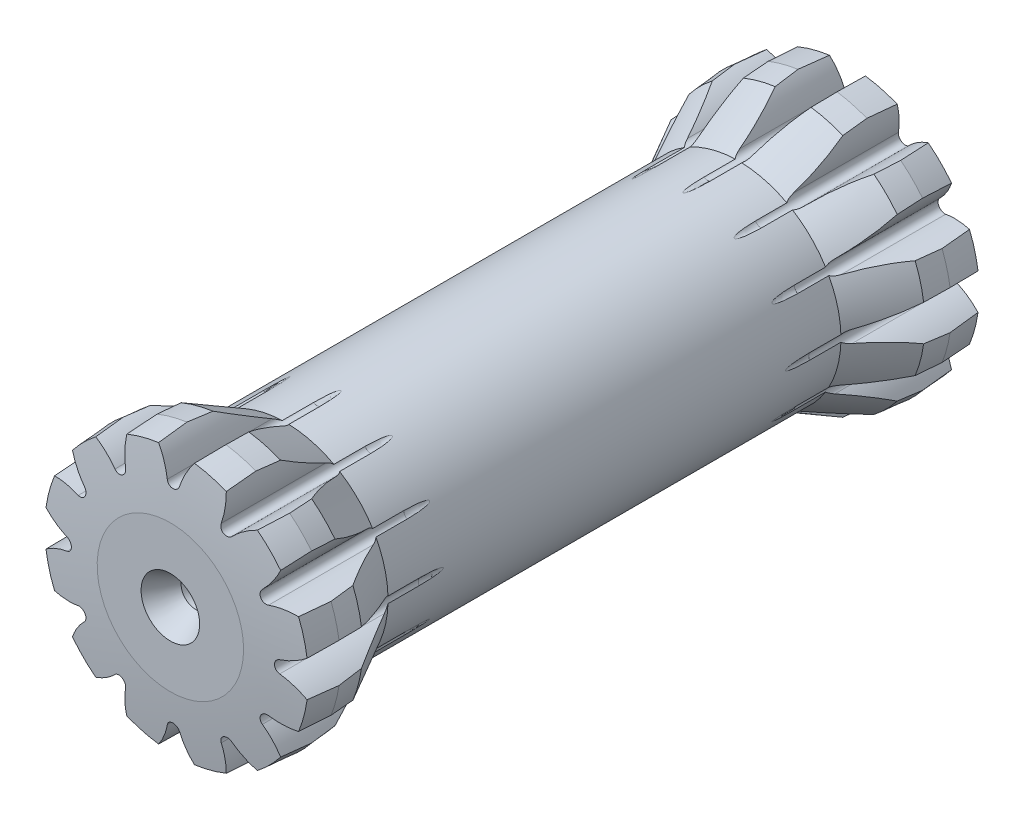
SolidWorks part; units mm, degrees
material "EN39B"
ref_plane "Front Plane" through (0, 0, 0) normal (0, 0, 1) x (1, 0, 0)
ref_plane "Top Plane" through (0, 0, 0) normal (0, 1, 0) x (1, 0, 0)
ref_plane "Right Plane" through (0, 0, 0) normal (1, 0, 0) x (0, 0, -1)
sketch "Sketch1" plane through (0, 0, 0) normal (1, 0, 0) x (0, 0, -1)
  line L0 (0, 0) -> (118.4245, 0) construction
  line L1 (0.6338, 13.5) -> (3.7, 13.725)
  line L2 (3.7, 13.725) -> (6.2, 13.5)
  line L3 (11.8, 10.5) -> (58.2, 10.5)
  line L4 (58.2, 10.5) -> (63.8, 13.5)
  line L5 (63.8, 13.5) -> (66.3, 13.725)
  line L6 (70, 0) -> (70, 7.5)
  line L7 (0, 0) -> (0, 7.5)
  line L8 (0, 0) -> (70, 0)
  line L9 (6.2, 13.5) -> (11.8, 10.5)
  line L11 (66.3, 13.725) -> (69.3662, 13.5)
  arc A0 (0, 7.5) -> (0.6338, 13.5) centre (99.7184, 0) cw
  arc A1 (70, 7.5) -> (69.3662, 13.5) centre (-29.7184, 0) ccw
  dimension "D7" = 100
  dimension "D8" = 15
  dimension "D10" = 100
  dimension "D12" = 6.2
  dimension "D2" = 3.7
  dimension "D3" = 6.2
  dimension "D4" = 3.7
  dimension "D5" = 11.8
  dimension "D6" = 21
  dimension "D9" = 70
  dimension "D11" = 15
  dimension "D13" = 27.45
  dimension "D14" = 11.8
  dimension "D15" = 27
revolve "Revolve1" add sketch "Sketch1" angle 360 about L0
sketch "Sketch2" plane through (0, 0, 0) normal (1, 0, 0) x (0, 0, -1)
  line L0 (70, 3) -> (67.4019, 1.5)
  line L1 (67.4019, 1.5) -> (64.9013, 1.5)
  line L2 (64.9013, 1.5) -> (64, 0)
  line L3 (0, 0) -> (41.5, 0) construction
  line L4 (70, -7.5) -> (70, 7.5) construction
  line L5 (70, 3) -> (70, 0)
  line L6 (64, 0) -> (70, 0)
  dimension "D1" = 3
  dimension "D2" = 30
  dimension "D3" = 59
  dimension "D4" = 6
  dimension "D5" = 6
revolve "Cut-Revolve1" cut sketch "Sketch2" angle 360 about L3
sketch "Sketch3" plane through (0, 0, 0) normal (1, 0, 0) x (0, 0, -1)
  line L0 (0, 3) -> (2.5981, 1.5)
  line L1 (2.5981, 1.5) -> (5.0987, 1.5)
  line L2 (5.0987, 1.5) -> (6, 0)
  line L3 (0, 3) -> (0, 0)
  line L4 (0, 0) -> (12.7492, 0) construction
  line L5 (6, 0) -> (0, 0)
  dimension "D1" = 6
  dimension "D2" = 30
  dimension "D3" = 59
  dimension "D4" = 3
  dimension "D5" = 6
revolve "Cut-Revolve2" cut sketch "Sketch3" angle 360 about L4
ref_plane "Plane1" through (0, 0, -85) normal (0, 0, 1) x (1, 0, 0)
sketch "Sketch4" plane through (0, 0, -70) normal (0, 0, 1) x (1, 0, 0)
  line L0 (0, 0) -> (-15.7466, 0) construction
  line L1 (0, 0) -> (0, 14.7663) construction
  arc A0 (-0.6292, 10.8869) -> (0.6292, 10.8869) centre (0, 11.05) ccw
  arc A2 (2, 13.5785) -> (-2, 13.5785) centre (0, 0) ccw
  arc A3 (-2, 13.5785) -> (-0.6292, 10.8869) centre (-7.4053, 9.1308) cw
  arc A4 (2, 13.5785) -> (0.6292, 10.8869) centre (7.4053, 9.1308) ccw
  circle A5 centre (0, 0) radius 13.725 construction
  dimension "D1" = 1.3
  dimension "D3" = 20.8
  dimension "D4" = 7
  dimension "D2" = 4
extrude "Cut-Extrude1" cut sketch "Sketch4" along normal blind 15
sketch "Sketch6" plane through (0, 0, -55) normal (0, 0, -1) x (-1, 0, 0)
  line L0 (-1.8382, 13.3743) -> (-1.8382, 15.404)
  line L1 (-1.8382, 15.404) -> (1.8382, 15.404)
  line L2 (1.8382, 15.404) -> (1.8382, 13.3743)
  line L3 (-8.4949, 41.05) -> (13.6472, 41.05) construction
  arc A0 (-0.6292, 10.8869) -> (-1.8382, 13.3743) centre (-7.4053, 9.1308) ccw construction
  arc A2 (1.8382, 13.3743) -> (0.6292, 10.8869) centre (7.4053, 9.1308) ccw construction
  arc A3 (-0.6292, 10.8869) -> (-1.8382, 13.3743) centre (-7.4053, 9.1308) ccw
  arc A4 (-0.6292, 10.8869) -> (0.6292, 10.8869) centre (0, 11.05) ccw
  arc A5 (1.8382, 13.3743) -> (0.6292, 10.8869) centre (7.4053, 9.1308) ccw
  arc A6 (-0.6292, 10.8869) -> (0.6292, 10.8869) centre (0, 11.05) ccw construction
  dimension "D1" = 30
revolve "Cut-Revolve3" cut sketch "Sketch6" angle 360 about L3
ref_axis "Axis1" through (0, 0, -58.2) along (0, 0, 1)
pattern_circular "CirPattern1" count 12 over 360 about axis through (0, 0, -58.2) along (0, 0, 1) of "Cut-Extrude1", "Cut-Revolve3"
sketch "Sketch5" plane through (0, 0, 0) normal (0, 0, 1) x (1, 0, 0)
  line L0 (0, 0) -> (20.7288, 0) construction
  line L1 (0, 0) -> (0, 13.7027) construction
  line L2 (-3, 14.5707) -> (-3, 15.1961)
  line L3 (-3, 15.1961) -> (3, 15.1961)
  line L4 (3, 14.5707) -> (3, 15.1961)
  arc A1 (-0.6292, 10.8869) -> (0.6292, 10.8869) centre (0, 11.05) ccw construction
  arc A2 (-0.6292, 10.8869) -> (-2, 13.5785) centre (-7.4053, 9.1308) ccw construction
  arc A3 (2, 13.5785) -> (0.6292, 10.8869) centre (7.4053, 9.1308) ccw construction
  arc A4 (-0.6292, 10.8869) -> (0.6292, 10.8869) centre (0, 11.05) ccw
  arc A7 (-0.6292, 10.8869) -> (-3, 14.5707) centre (-7.4053, 9.1308) ccw
  arc A8 (3, 14.5707) -> (0.6292, 10.8869) centre (7.4053, 9.1308) ccw
  dimension "D1" = 6
  dimension "D2" = 15.1961
extrude "Cut-Extrude2" cut sketch "Sketch5" against normal blind 15
sketch "Sketch8" plane through (0, 0, -15) normal (0, 0, 1) x (1, 0, 0)
  line L0 (-13.6472, 41.05) -> (11.7246, 41.05) construction
  line L1 (1.8382, 13.3743) -> (1.8382, 15.404) construction
  line L2 (1.8382, 15.404) -> (-1.8382, 15.404) construction
  line L3 (-1.8382, 15.404) -> (-1.8382, 13.3743) construction
  line L4 (1.8382, 13.3743) -> (1.8382, 15.404)
  line L5 (1.8382, 15.404) -> (-1.8382, 15.404)
  line L6 (-1.8382, 15.404) -> (-1.8382, 13.3743)
  arc A0 (-0.6292, 10.8869) -> (-1.8382, 13.3743) centre (-7.4053, 9.1308) ccw construction
  arc A1 (1.8382, 13.3743) -> (0.6292, 10.8869) centre (7.4053, 9.1308) ccw construction
  arc A2 (-0.6292, 10.8869) -> (0.6292, 10.8869) centre (0, 11.05) ccw construction
  arc A3 (-0.6292, 10.8869) -> (-1.8382, 13.3743) centre (-7.4053, 9.1308) ccw
  arc A4 (1.8382, 13.3743) -> (0.6292, 10.8869) centre (7.4053, 9.1308) ccw
  arc A5 (-0.6292, 10.8869) -> (0.6292, 10.8869) centre (0, 11.05) ccw
revolve "Cut-Revolve5" cut sketch "Sketch8" angle 360 about L0
pattern_circular "CirPattern2" count 12 over 360 about axis through (0, 0, -58.2) along (0, 0, 1) of "Cut-Extrude2", "Cut-Revolve5"
